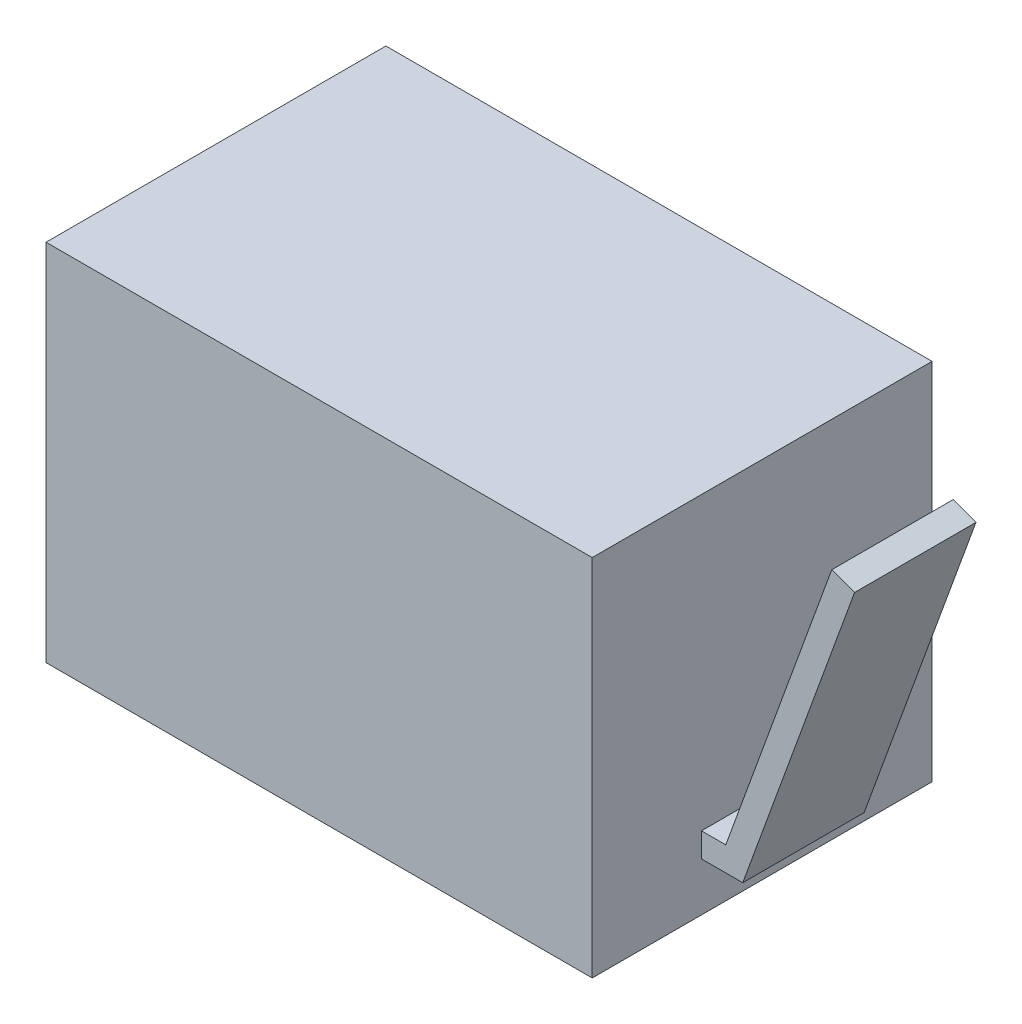
SolidWorks part; units mm, degrees
ref_plane "Front Plane" through (0, 0, 0) normal (0, 0, 1) x (1, 0, 0)
ref_plane "Top Plane" through (0, 0, 0) normal (0, 1, 0) x (1, 0, 0)
ref_plane "Right Plane" through (0, 0, 0) normal (1, 0, 0) x (0, 0, -1)
sketch "Sketch1" plane through (0, 0, 0) normal (0, 1, 0) x (1, 0, 0)
  line L1 (-22.5, 14) -> (22.5, 14)
  line L2 (-22.5, 14) -> (-22.5, -14)
  line L3 (-22.5, -14) -> (22.5, -14)
  line L4 (22.5, 14) -> (22.5, -14)
  line L5 (-22.5, 14) -> (22.5, -14) construction
  line L6 (-22.5, -14) -> (22.5, 14) construction
  point P0 (0, 0)
  dimension "D1" = 45
  dimension "D2" = 28
extrude "Boss-Extrude1" add sketch "Sketch1" along normal blind 30
sketch "Sketch2" plane through (0, 0, 0) normal (0, 0, 1) x (1, 0, 0)
  line L0 (22.5, 4) -> (25.9004, 4)
  line L1 (25.9004, 4) -> (35.1147, 29.316)
  line L2 (35.1147, 29.316) -> (33.2353, 30)
  line L3 (33.2353, 30) -> (24.5, 6)
  line L4 (24.5, 6) -> (22.5, 6)
  line L5 (22.5, 6) -> (22.5, 4)
  line L6 (22.5, 30) -> (22.5, 0) construction
  line L7 (22.5, 30) -> (-22.5, 30) construction
  dimension "D1" = 2
  dimension "D2" = 2
  dimension "D3" = 110
  dimension "D4" = 4
extrude "Boss-Extrude2" add sketch "Sketch2" along normal blind 5 and the other way blind 5
ref_plane "Alignment Plane" through (0, 0, -19.05) normal (0, 0, 1) x (1, 0, 0)
sketch "Sketch3" plane through (0, 0, 0) normal (0, 1, 0) x (1, 0, 0)
  point P0 (30, 0)
  dimension "D1" = 30
ref_axis "Axis1" through (30, 0, 0) along (0, 1, 0)
